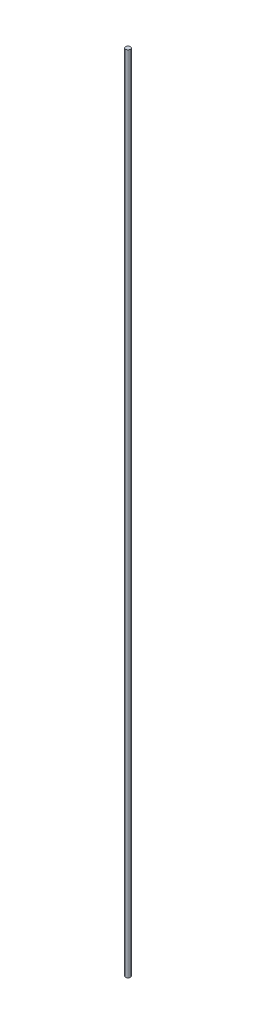
SolidWorks part; units mm, degrees
ref_plane "Спереди" through (0, 0, 0) normal (0, 0, 1) x (1, 0, 0)
ref_plane "Сверху" through (0, 0, 0) normal (0, 1, 0) x (1, 0, 0)
ref_plane "Справа" through (0, 0, 0) normal (1, 0, 0) x (0, 0, -1)
sketch "Эскиз2" plane through (0, 0, 0) normal (0, 0, 1) x (1, 0, 0)
  line L5 (-2.5, 422.3) -> (0, 422.3)
  line L6 (-2.5, 422.3) -> (-2.5, -422.3)
  line L7 (-2.5, -422.3) -> (0, -422.3)
  line L8 (0, 422.3) -> (0, -422.3)
  line L9 (-2.5, 422.3) -> (0, -422.3) construction
  line L10 (-2.5, -422.3) -> (0, 422.3) construction
  point P0 (-1.25, 0)
  point P5 (0, 0)
  dimension "D1" = 2.5
  dimension "D2" = 844.6
revolve "Повернуть1" add sketch "Эскиз2" angle 360 about L6
equation "\"Ширина груза\"= 420"
equation "\"Глубина груза\"= 490"
equation "\"Высота груза\"= 297"
equation "\"Ширина ячейки\"= \"Ширина груза\" + 10"
equation "\"Глубина ячейки\"= \"Глубина груза\" + 10"
equation "\"Высота ячейки\"= \"Высота груза\" + 10 + 13"
equation "\"Колво ячеек ширина\"= 2"
equation "\"Колво ячеек высота\"= 2"
equation "\"Толщина стенки\"= 10"
equation "\"Крепление дверцы\"= 5"
equation "\"Ширина рейки\"= \"Толщина шестерни\""
equation "\"Высота рейки\"= 20"
equation "\"Высота пола\"= 20"
equation "\"Колво полозьев\"= 5"
equation "\"Отступ рейки\"= 20"
equation "\"Глубина каретки\"= \"Глубина ячейки\" + 30 + \"Мотор Y высота корпуса\" + 20"
equation "\"Длинна рейки\"= ( \"Ширина ячейки\" + \"Толщина стенки\" + \"Крепление дверцы\" ) * \"Колво ячеек ширина\" + \"Ширина ячейки выгрузки\" * \"Колво выгрузки\" + \"Толщина стенки\""
equation "\"Отступ шпильки\"= 20"
equation "\"Диаметр шпильки\"= 5"
equation "\"Длинна шпильки\"= ( \"Высота ячейки\" + \"Толщина стенки\" + \"Высота пола\" ) * \"Колво ячеек высота\" + ( \"Толщина стенки\" + \"Отступ рейки\" ) * 2 "
equation "\"D1@Эскиз2\"= \"Диаметр шпильки\" / 2"
equation "\"D2@Эскиз2\"=\"Длинна шпильки\" + \"Мотор X ширина корпуса\" + \"Мотор Y ширина корпуса\""
equation "\"Ширина пластины\"= 50  "
equation "\"Высота зона выгрузки\"= \"Высота ячейки\" * 2 + \"Толщина стенки\" * 2"
equation "\"Колво выгрузки\"= 1"
equation "\"Отступ крепления мотора фиксации\" = 30"
equation "\"Мотор X ширина корпуса\"= 42.3"
equation "\"Мотор X высота корпуса\"= 42.3"
equation "\"Мотор X длина корпуса\"= 40"
equation "\"Мотор X вылет вала\"= 19.8"
equation "\"Мотор Y ширина корпуса\"= 42.3"
equation "\"Мотор Y высота корпуса\"= 42.3"
equation "\"Мотор Y длина корпуса\"= 48"
equation "\"Мотор Y вылет вала\"= 30"
equation "\"Мотор Z ширина корпуса\"= 42"
equation "\"Мотор Z высота корпуса\"= 42"
equation "\"Мотор Z длина корпуса\"= 40"
equation "\"Мотор Z вылет вала\"= 23"
equation "\"Мотор диаметр вала ПРЕДВ\"= 5"
equation "\"Мотор шаг крепления ПРЕДВ\"= 31"
equation "\"Мотор диаметр отверстий ПРЕДВ\"= 3"
equation "\"Мотор глубина отверстий ПРЕДВ\"= 4.5"
equation "\"Мотор диаметр буртика ПРЕДВ\"= 22"
equation "\"Мотор высота буртика ПРЕДВ\"= 2"
equation "\"Мотор диаметр шкива ПРЕДВ\"= 16"
equation "\"Мотор длина шкива ПРЕДВ\"= 12"
equation "\"Мотор отступ шкива ПРЕДВ\"= 5"
equation "\"Мотор X шаг градусов\"= 1.8"
equation "\"Мотор X ток А\"= 1.5"
equation "\"Мотор X сопротивление Ом\"= 1.3"
equation "\"Мотор X индуктивность мГн\"= 2"
equation "\"Мотор Y шаг градусов\"= 1.8"
equation "\"Мотор Y ток А\"= 2.2"
equation "\"Мотор Y сопротивление Ом\"= 0.9"
equation "\"Мотор Y индуктивность мГн\"= 2"
equation "\"Мотор Z шаг градусов\"= 1.8"
equation "\"Мотор Z ток А\"= 1"
equation "\"Мотор Z сопротивление Ом\"= 4"
equation "\"Мотор Z индуктивность мГн\"= 8"
equation "\"Мотор Y диаметр ротора\"= 25.78"
equation "\"Ширина ячейки выгрузки\"= \"Ширина ячейки\" + \"Толщина стенки\" + \"Отступ крепления мотора фиксации\"*2"
